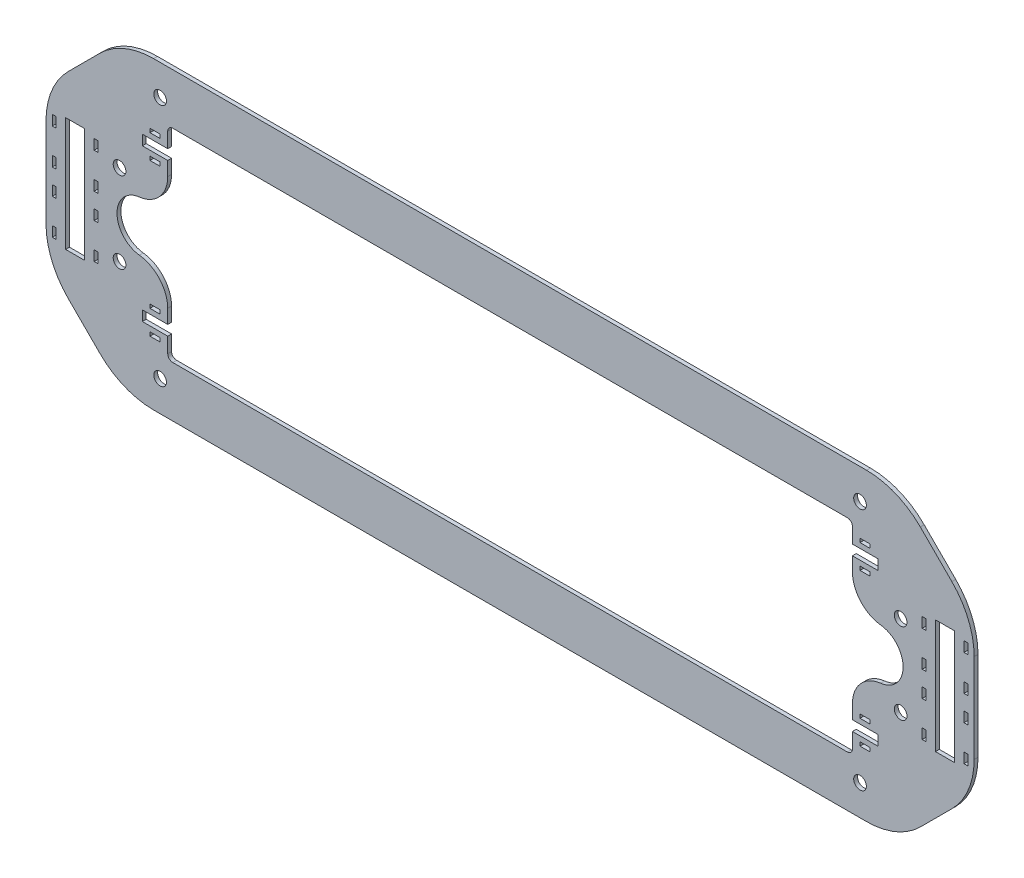
SolidWorks part; units mm, degrees
material "5052-H32"
ref_plane "Front Plane" through (0, 0, 0) normal (0, 0, 1) x (1, 0, 0)
ref_plane "Top Plane" through (0, 0, 0) normal (0, 1, 0) x (1, 0, 0)
ref_plane "Right Plane" through (0, 0, 0) normal (1, 0, 0) x (0, 0, -1)
sketch "Sketch2" plane through (0, 0, 0) normal (0, 0, 1) x (1, 0, 0)
  line L8 (183, -35) -> (183, 35)
  line L9 (158, 60) -> (-158, 60)
  line L10 (-183, 35) -> (-183, -35)
  line L11 (-158, -60) -> (158, -60)
  line L52 (135, -28) -> (135, -22.5)
  line L53 (145, -28) -> (135, -28)
  line L54 (145, -32) -> (145, -28)
  line L55 (135, -32) -> (145, -32)
  line L56 (135, -38) -> (135, -32)
  line L57 (-133, -40) -> (133, -40)
  line L58 (-135, -32) -> (-135, -38)
  line L59 (-145, -32) -> (-135, -32)
  line L60 (-145, -28) -> (-145, -32)
  line L61 (-135, -28) -> (-145, -28)
  line L62 (-135, -22.5) -> (-135, -28)
  line L63 (-135, 28) -> (-135, 22.5)
  line L64 (-145, 28) -> (-135, 28)
  line L65 (-145, 32) -> (-145, 28)
  line L66 (-135, 32) -> (-145, 32)
  line L67 (-135, 38) -> (-135, 32)
  line L68 (133, 40) -> (-133, 40)
  line L69 (135, 32) -> (135, 38)
  line L70 (145, 32) -> (135, 32)
  line L71 (145, 28) -> (145, 32)
  line L72 (135, 28) -> (145, 28)
  line L73 (135, 22.5) -> (135, 28)
  arc A8 (183, 35) -> (158, 60) centre (158, 35) ccw
  arc A9 (-158, 60) -> (-183, 35) centre (-158, 35) ccw
  arc A10 (-183, -35) -> (-158, -60) centre (-158, -35) ccw
  arc A11 (158, -60) -> (183, -35) centre (158, -35) ccw
  arc A28 (146.1724, -9.931) -> (135, -22.5) centre (147.6562, -22.5) ccw
  arc A29 (133, -40) -> (135, -38) centre (133, -38) ccw
  arc A30 (-135, -38) -> (-133, -40) centre (-133, -38) ccw
  arc A31 (-135, -22.5) -> (-146.1724, -9.931) centre (-147.6562, -22.5) ccw
  arc A32 (-146.1724, 9.931) -> (-146.1724, -9.931) centre (-145, 0) ccw
  arc A33 (-146.1724, 9.931) -> (-135, 22.5) centre (-147.6562, 22.5) ccw
  arc A34 (-133, 40) -> (-135, 38) centre (-133, 38) ccw
  arc A35 (135, 38) -> (133, 40) centre (133, 38) ccw
  arc A36 (135, 22.5) -> (146.1724, 9.931) centre (147.6562, 22.5) ccw
  arc A37 (146.1724, -9.931) -> (146.1724, 9.931) centre (145, 0) ccw
  dimension "D5" = 25
  dimension "D12" = 2
  dimension "D13" = 145
  dimension "D4" = 10
  dimension "D9" = 12.6562
  dimension "D1" = 120
  dimension "D2" = 366
  dimension "D3" = 183
  dimension "D6" = 20
  dimension "D7" = 20
  dimension "D8" = 290
  dimension "D10" = 6
  dimension "D11" = 4
base flange "Base-Flange1" sketch "Sketch2" thickness 1.5189 reverse thickness direction no parameters "D1"=1.905
sketch "Sketch7" plane through (0, 0, 0) normal (0, 0, 1) x (1, 0, 0)
  line L0 (-135, 32) -> (-145, 32) construction
  line L1 (-164, 21) -> (-162.5, 21)
  line L2 (-145, -32) -> (-135, -32) construction
  line L3 (-158, -60) -> (158, -60) construction
  line L4 (-183, 35) -> (-183, -35) construction
  line L5 (183, -35) -> (183, 35) construction
  line L8 (-180.5, 21) -> (-180.5, 17)
  line L9 (-179, 21) -> (-180.5, 21)
  line L10 (-179, 17) -> (-179, 21)
  line L11 (-180.5, 17) -> (-179, 17)
  line L16 (-164, 21) -> (-164, 17)
  line L17 (-162.5, 21) -> (-164, 21)
  line L18 (-162.5, 17) -> (-162.5, 21)
  line L19 (-164, 17) -> (-162.5, 17)
  line L24 (-179, 3) -> (-179, 7)
  line L25 (-180.5, 3) -> (-179, 3)
  line L26 (-180.5, 7) -> (-180.5, 3)
  line L27 (-179, 7) -> (-180.5, 7)
  line L32 (-162.5, 3) -> (-162.5, 7)
  line L33 (-164, 3) -> (-162.5, 3)
  line L34 (-164, 7) -> (-164, 3)
  line L35 (-162.5, 7) -> (-164, 7)
  line L40 (-164, -3) -> (-164, -7)
  line L41 (-162.5, -3) -> (-164, -3)
  line L42 (-162.5, -7) -> (-162.5, -3)
  line L43 (-164, -7) -> (-162.5, -7)
  line L48 (-180.5, -7) -> (-179, -7)
  line L49 (-180.5, -3) -> (-180.5, -7)
  line L50 (-179, -3) -> (-180.5, -3)
  line L51 (-179, -7) -> (-179, -3)
  line L56 (-162.5, -21) -> (-162.5, -17)
  line L57 (-164, -21) -> (-162.5, -21)
  line L58 (-164, -17) -> (-164, -21)
  line L59 (-162.5, -17) -> (-164, -17)
  line L64 (-179, -17) -> (-180.5, -17)
  line L65 (-179, -21) -> (-179, -17)
  line L66 (-180.5, -21) -> (-179, -21)
  line L67 (-180.5, -17) -> (-180.5, -21)
  line L72 (-138, -24.5) -> (-142, -24.5)
  line L73 (-138, -26) -> (-138, -24.5)
  line L74 (-142, -26) -> (-138, -26)
  line L75 (-142, -24.5) -> (-142, -26)
  line L80 (-142, -34) -> (-142, -35.5)
  line L81 (-138, -34) -> (-142, -34)
  line L82 (-138, -35.5) -> (-138, -34)
  line L83 (-142, -35.5) -> (-138, -35.5)
  line L88 (162.5, -17) -> (162.5, -21)
  line L89 (164, -17) -> (162.5, -17)
  line L90 (164, -21) -> (164, -17)
  line L91 (162.5, -21) -> (164, -21)
  line L96 (164, -7) -> (164, -3)
  line L97 (162.5, -7) -> (164, -7)
  line L98 (162.5, -3) -> (162.5, -7)
  line L99 (164, -3) -> (162.5, -3)
  line L104 (142, -24.5) -> (138, -24.5)
  line L105 (142, -26) -> (142, -24.5)
  line L106 (138, -26) -> (142, -26)
  line L107 (138, -24.5) -> (138, -26)
  line L112 (142, -35.5) -> (142, -34)
  line L113 (138, -35.5) -> (142, -35.5)
  line L114 (138, -34) -> (138, -35.5)
  line L115 (142, -34) -> (138, -34)
  line L120 (180.5, -17) -> (179, -17)
  line L121 (180.5, -21) -> (180.5, -17)
  line L122 (179, -21) -> (180.5, -21)
  line L123 (179, -17) -> (179, -21)
  line L128 (179, -7) -> (180.5, -7)
  line L129 (179, -3) -> (179, -7)
  line L130 (180.5, -3) -> (179, -3)
  line L131 (180.5, -7) -> (180.5, -3)
  line L136 (162.5, 21) -> (162.5, 17)
  line L137 (164, 21) -> (162.5, 21)
  line L138 (164, 17) -> (164, 21)
  line L139 (162.5, 17) -> (164, 17)
  line L144 (164, 3) -> (164, 7)
  line L145 (162.5, 3) -> (164, 3)
  line L146 (162.5, 7) -> (162.5, 3)
  line L147 (164, 7) -> (162.5, 7)
  line L152 (180.5, 7) -> (179, 7)
  line L153 (180.5, 3) -> (180.5, 7)
  line L154 (179, 3) -> (180.5, 3)
  line L155 (179, 7) -> (179, 3)
  line L160 (179, 17) -> (180.5, 17)
  line L161 (179, 21) -> (179, 17)
  line L162 (180.5, 21) -> (179, 21)
  line L163 (180.5, 17) -> (180.5, 21)
  line L168 (142, 34) -> (142, 35.5)
  line L169 (138, 34) -> (142, 34)
  line L170 (138, 35.5) -> (138, 34)
  line L171 (142, 35.5) -> (138, 35.5)
  line L176 (138, 24.5) -> (142, 24.5)
  line L177 (138, 26) -> (138, 24.5)
  line L178 (142, 26) -> (138, 26)
  line L179 (142, 24.5) -> (142, 26)
  line L184 (-138, 34) -> (-138, 35.5)
  line L185 (-142, 34) -> (-138, 34)
  line L186 (-142, 35.5) -> (-142, 34)
  line L187 (-138, 35.5) -> (-142, 35.5)
  line L192 (-142, 26) -> (-142, 24.5)
  line L193 (-138, 26) -> (-142, 26)
  line L194 (-138, 24.5) -> (-138, 26)
  line L195 (-142, 24.5) -> (-138, 24.5)
  circle A2 centre (-154, 16) radius 2.5
  circle A4 centre (-154, -16) radius 2.5
  circle A6 centre (-138, -48) radius 2.5
  circle A8 centre (-138, 48) radius 2.5
  circle A10 centre (138, -48) radius 2.5
  circle A12 centre (154, -16) radius 2.5
  circle A14 centre (154, 16) radius 2.5
  circle A16 centre (138, 48) radius 2.5
  dimension "D1" = 5
  dimension "D2" = 16
  dimension "D3" = 32
  dimension "D4" = 16
  dimension "D5" = 32
  dimension "D6" = 16
  dimension "D7" = 154
  dimension "D8" = 308
  dimension "D9" = 16
  dimension "D10" = 16.5
  dimension "D11" = 1.5
  dimension "D12" = 4
  dimension "D13" = 9.5
  dimension "D14" = 2
  dimension "D15" = 2
  dimension "D16" = 9.5
  dimension "D17" = 14
  dimension "D18" = 14
  dimension "D19" = 6
  dimension "D20" = 39
  dimension "D21" = 2.5
  dimension "D22" = 2.5
  dimension "D23" = 15
extrude "Cut-Extrude1" cut sketch "Sketch7" against normal blind 10 contours A2 | L16 L19 L18 L1 | L8 L11 L10 L9 | L24 L27 L26 L25 | L48 L51 L50 L49 | L40 L43 L42 L41 | L32 L35 L34 L33 | L192 L195 L194 L193 | L184 L187 L186 L185 | A4 | L56 L59 L58 L57 | L64 L67 L66 L65 | L72 L75 L74 L73 | L80 L83 L82 L81 | A6 | A8 | L88 L91 L90 L89 | A12 | L104 L107 L106 L105 | L112 L115 L114 L113 | A10 | L120 L123 L122 L121 | L128 L131 L130 L129 | L96 L99 L98 L97 | L144 L147 L146 L145 | A14 | L136 L139 L138 L137 | L160 L163 L162 L161 | L152 L155 L154 L153 | L176 L179 L178 L177 | L168 L171 L170 L169 | A16
sketch "Sketch8" plane through (0, 0, -1.5189) normal (0, 0, -1) x (-1, 0, 0)
  line L0 (0, 0) -> (0, -40) construction
  line L1 (-175.25, -22.5) -> (-167.75, -22.5)
  line L2 (-175.25, -22.5) -> (-175.25, 22.5)
  line L3 (-175.25, 22.5) -> (-167.75, 22.5)
  line L4 (-167.75, -22.5) -> (-167.75, 22.5)
  line L5 (-171.5, 22.5) -> (-171.5, -22.5) construction
  line L6 (-175.25, 0) -> (-167.75, 0) construction
  line L7 (133, -40) -> (-133, -40) construction
  line L8 (175.25, 0) -> (167.75, 0) construction
  line L9 (171.5, 22.5) -> (171.5, -22.5) construction
  line L10 (167.75, -22.5) -> (167.75, 22.5)
  line L11 (175.25, 22.5) -> (167.75, 22.5)
  line L12 (175.25, -22.5) -> (175.25, 22.5)
  line L13 (175.25, -22.5) -> (167.75, -22.5)
  point P0 (-171.5, 0)
  point P16 (171.5, 0)
  dimension "D1" = 343
  dimension "D2" = 45
  dimension "D3" = 7.5
extrude "Cut-Extrude2" cut sketch "Sketch8" against normal blind 1.5189 normal cut yes
sketch "Sketch9" plane through (0, 0, -1.5189) normal (0, 0, -1) x (-1, 0, 0)
  line L0 (-183, 30) -> (-153, 60)
  line L1 (0, 0) -> (0, -50000) construction
  line L2 (0, 0) -> (50000, 0) construction
  line L3 (-183, -35) -> (-183, 35) construction
  line L4 (-158, -60) -> (158, -60)
  line L5 (183, -35) -> (183, 35)
  line L6 (158, 60) -> (-158, 60)
  line L7 (-183, 35) -> (-183, -35)
  line L8 (-158, -60) -> (158, -60)
  line L9 (183, -35) -> (183, 35)
  line L10 (158, 60) -> (-158, 60)
  line L11 (-183, 35) -> (-183, -35)
  line L12 (183, 30) -> (153, 60)
  line L13 (183, -30) -> (153, -60)
  line L14 (-183, -30) -> (-153, -60)
  arc A4 (-183, -35) -> (-158, -60) centre (-158, -35) ccw
  arc A5 (158, -60) -> (183, -35) centre (158, -35) ccw
  arc A6 (183, 35) -> (158, 60) centre (158, 35) ccw
  arc A7 (-158, 60) -> (-183, 35) centre (-158, 35) ccw
  arc A8 (-183, -35) -> (-158, -60) centre (-158, -35) ccw
  arc A9 (158, -60) -> (183, -35) centre (158, -35) ccw
  arc A10 (183, 35) -> (158, 60) centre (158, 35) ccw
  arc A11 (-158, 60) -> (-183, 35) centre (-158, 35) ccw
  dimension "D2" = 30
  dimension "D3" = 45
  dimension "D1" = 0
extrude "Cut-Extrude3" cut sketch "Sketch9" against normal blind 10 contours L10 A11 L11 L0 | L11 A8 L8 L14 | L8 A9 L9 L13 | L9 A10 L10 L12 normal cut yes
fillet "Fillet1" radius 30 8 edges at (153, -60, -0.7595) (183, -30, -0.7595) (183, 30, -0.7595) (153, 60, -0.7595) (-183, 30, -0.7595) (-153, 60, -0.7595) (-183, -30, -0.7595) (-153, -60, -0.7595)
sketch "Bend-Lines1" [suppressed] plane through (0, 0, 0) normal (0, 1, 0) x (1, 0, 0)
sketch "Bounding-Box1" [suppressed] plane through (0, 0, 0) normal (0, 1, 0) x (1, 0, 0)
sheet metal parameters "Sheet-Metal1" thickness 1.5189 parameters "D1"=1.905
flat pattern "Flat-Pattern1" [suppressed]
sketch "Bend-Lines2" plane through (0, 0, 0) normal (0, 1, 0) x (1, 0, 0)
sketch3d "Bounding-Box2" [suppressed]
  line L0 (-341, 95, 0) -> (25, 95, 0) construction
  line L1 (-341, -25, 0) -> (25, -25, 0) construction
  line L2 (-341, 95, 0) -> (-341, -25, 0) construction
  line L3 (25, 95, 0) -> (25, -25, 0) construction
sheet metal parameters "Sheet-Metal2" thickness 1.5189 parameters "D1"=1.905
flat pattern "Flat-Pattern1"
sketch "Bend-Lines2" plane through (0, 0, 0) normal (0, 1, 0) x (1, 0, 0)
sketch3d "Bounding-Box2" [suppressed]
  line L0 (-341, 95, 0) -> (25, 95, 0) construction
  line L1 (-341, -25, 0) -> (25, -25, 0) construction
  line L2 (-341, 95, 0) -> (-341, -25, 0) construction
  line L3 (25, 95, 0) -> (25, -25, 0) construction
sheet metal parameters "Sheet-Metal3" thickness 1.5189 parameters "D1"=1.905
flat pattern "Flat-Pattern1"
sketch "Bend-Lines2" plane through (0, 0, 0) normal (0, 1, 0) x (1, 0, 0)
sketch3d "Bounding-Box2" [suppressed]
  line L0 (-341, 95, 0) -> (25, 95, 0) construction
  line L1 (-341, -25, 0) -> (25, -25, 0) construction
  line L2 (-341, 95, 0) -> (-341, -25, 0) construction
  line L3 (25, 95, 0) -> (25, -25, 0) construction
sheet metal parameters "Sheet-Metal4" thickness 1.5189 parameters "D1"=1.905
flat pattern "Flat-Pattern1"
sketch "Bend-Lines2" plane through (0, 0, 0) normal (0, 1, 0) x (1, 0, 0)
sketch3d "Bounding-Box2" [suppressed]
  line L0 (-341, 95, 0) -> (25, 95, 0) construction
  line L1 (-341, -25, 0) -> (25, -25, 0) construction
  line L2 (-341, 95, 0) -> (-341, -25, 0) construction
  line L3 (25, 95, 0) -> (25, -25, 0) construction
